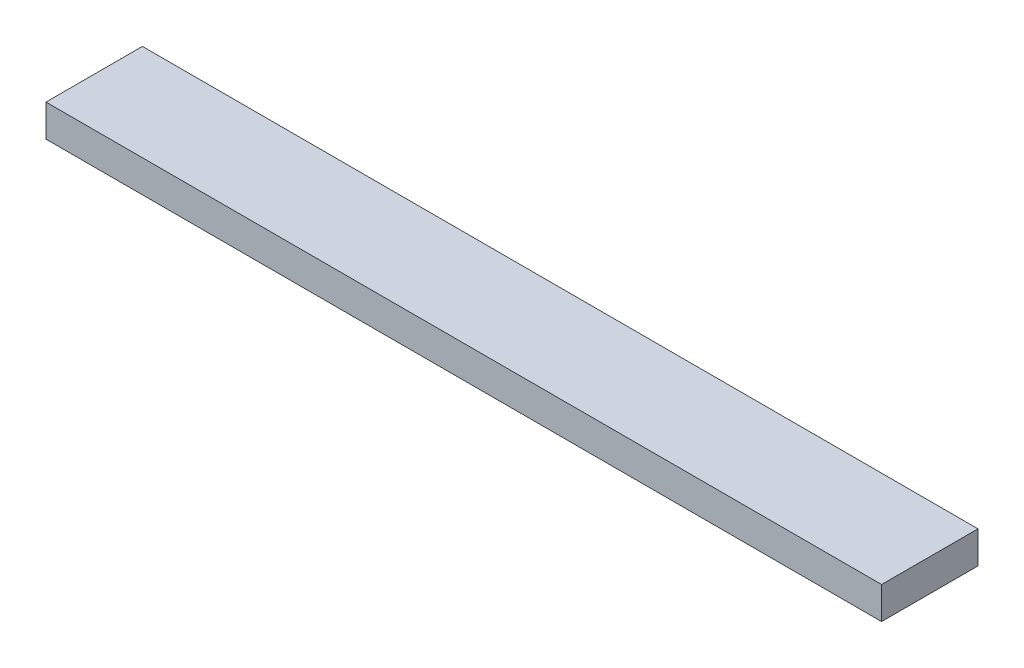
SolidWorks part; units mm, degrees
material "PET"
ref_plane "Front Plane" through (0, 0, 0) normal (0, 0, 1) x (1, 0, 0)
ref_plane "Top Plane" through (0, 0, 0) normal (0, 1, 0) x (1, 0, 0)
ref_plane "Right Plane" through (0, 0, 0) normal (1, 0, 0) x (0, 0, -1)
sketch "CrossSection" plane through (0, 0, 0) normal (1, 0, 0) x (0, 0, -1)
  line L1 (-9.525, 3.175) -> (9.525, 3.175)
  line L2 (-9.525, 3.175) -> (-9.525, -3.175)
  line L3 (-9.525, -3.175) -> (9.525, -3.175)
  line L4 (9.525, 3.175) -> (9.525, -3.175)
  line L5 (-9.525, 3.175) -> (9.525, -3.175) construction
  line L6 (-9.525, -3.175) -> (9.525, 3.175) construction
  point P0 (0, 0)
  dimension "D1" = 6.35
  dimension "D2" = 19.05
extrude "1/4 Inch Thickness" add sketch "CrossSection" along normal mid plane 165.1
sketch "Support Span" plane through (0, 0, 0) normal (0, 1, 0) x (1, 0, 0)
  line L0 (0, 0) -> (50.8, 0) construction
  line L1 (0, 0) -> (-50.8, 0) construction
  line L2 (50.8, 9.525) -> (50.8, -9.525) construction
  line L3 (82.55, 9.525) -> (-82.55, 9.525) construction
  line L4 (82.55, -9.525) -> (-82.55, -9.525) construction
  line L5 (-50.8, 9.525) -> (-50.8, -9.525) construction
  dimension "D1" = 50.8
  dimension "D2" = 101.6
ref_plane "Support 1" through (50.8, 0, 0) normal (1, 0, 0) x (0, 0, -1)
ref_plane "Support 2" through (-50.8, 0, 0) normal (1, 0, 0) x (0, 0, -1)
equation "\"D1@Support Span\" = \"D1@CrossSection\" * 8"
equation "\"D2@Support Span\" = \"D1@CrossSection\" * 16"
